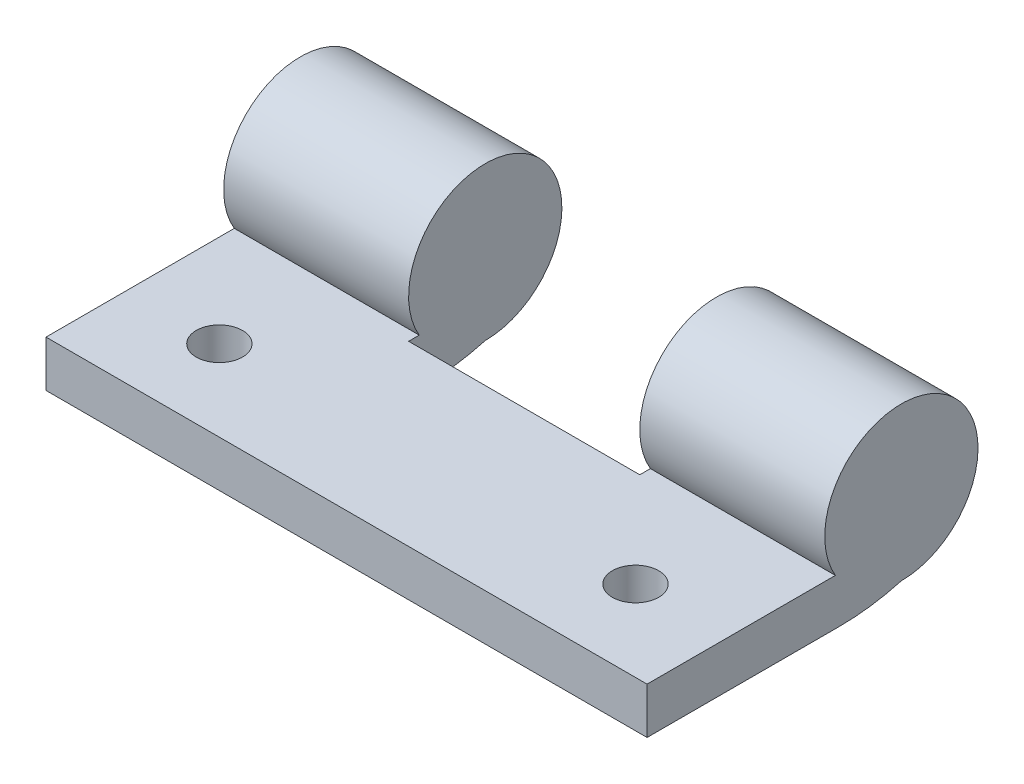
SolidWorks part; units mm, degrees
material "ABS"
ref_plane "前视基准面" through (0, 0, 0) normal (0, 0, 1) x (1, 0, 0)
ref_plane "上视基准面" through (0, 0, 0) normal (0, 1, 0) x (1, 0, 0)
ref_plane "右视基准面" through (0, 0, 0) normal (1, 0, 0) x (0, 0, -1)
sketch "草图1" plane through (0, 0, 0) normal (0, 1, 0) x (1, 0, 0)
  line L0 (0, 0) -> (0, -7.5) construction
  line L1 (-22.1376, 0) -> (22.1376, 0) construction
  line L2 (-13, -11) -> (13, -11)
  line L3 (13, -11) -> (13, 0)
  line L4 (13, 0) -> (-13, 0)
  line L5 (-9, -7.5) -> (9, -7.5) construction
  line L6 (-13, -11) -> (-13, 0)
  circle A0 centre (9, -7.5) radius 1
  circle A1 centre (-9, -7.5) radius 1
  point P14 (0, -11)
  dimension "D5" = 2
  dimension "D1" = 13
  dimension "D2" = 22
  dimension "D3" = 7.5
  dimension "D4" = 9
extrude "凸台-拉伸1" add sketch "草图1" along normal blind 2
sketch "草图2" plane through (13, 0, 0) normal (1, 0, 0) x (0, 0, -1)
  line L0 (0, 0) -> (0, 7) construction
  circle A0 centre (0, 3.685) radius 3.315
  dimension "D2" = 6.63
  dimension "D1" = 7
extrude "凸台-拉伸2" add sketch "草图2" against normal up to surface (26 mm away) up to face at (-13, 1, 5.5)
fillet "圆角1" radius 10 1 edges at (0, 0, 0)
sketch "草图3" plane through (0, 2, 0) normal (0, 1, 0) x (1, 0, 0)
  line L0 (0, 3.685) -> (0, 8.821) construction
  line L1 (-5, 3.685) -> (5, 3.685)
  line L2 (5, 3.685) -> (5, -3.315)
  line L3 (-13, -3.315) -> (13, -3.315) construction
  line L4 (5, -3.315) -> (-5, -3.315)
  line L6 (-5, 3.685) -> (-5, -3.315)
  line L7 (0, 3.685) -> (0, 0) construction
  dimension "D1" = 10
  dimension "D2" = 7
extrude "切除-拉伸1" cut sketch "草图3" against normal through all both and the other way through all
